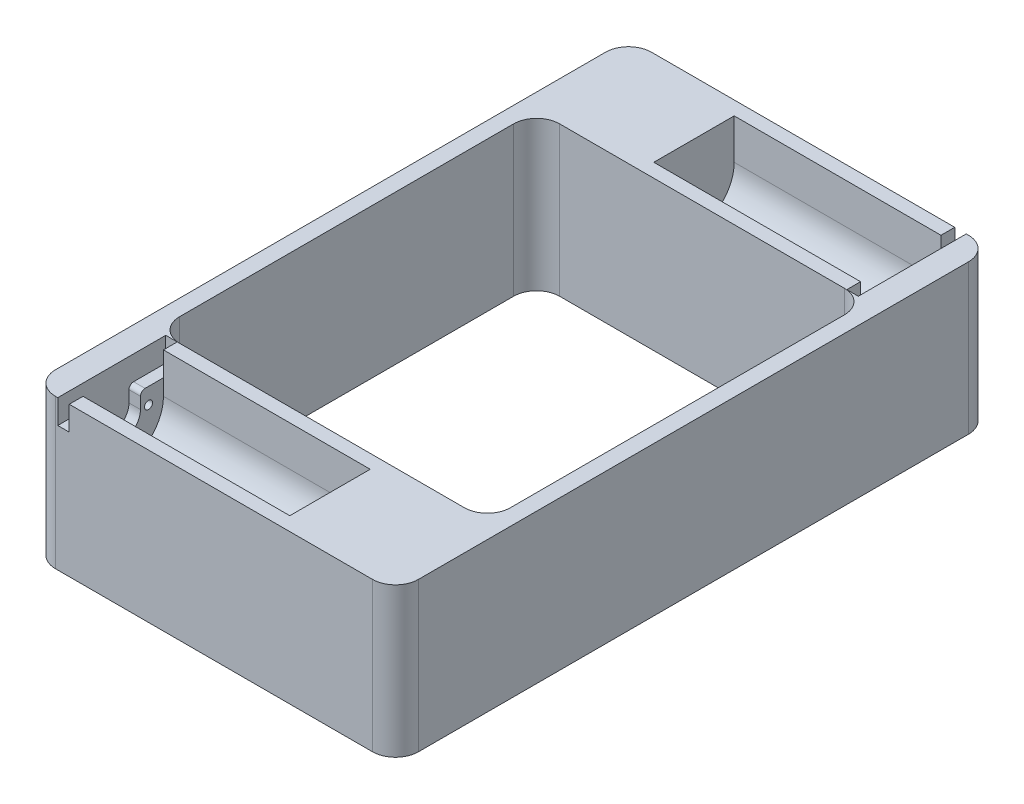
SolidWorks part; units mm, degrees
ref_plane "Front Plane" through (0, 0, 0) normal (0, 0, 1) x (1, 0, 0)
ref_plane "Top Plane" through (0, 0, 0) normal (0, 1, 0) x (1, 0, 0)
ref_plane "Right Plane" through (0, 0, 0) normal (1, 0, 0) x (0, 0, -1)
ref_axis "Center Axis" through (0, 23.7128, 0) along (0, -1, 0)
sketch "Sketch1" plane through (0, 0, 0) normal (1, 0, 0) x (0, 0, -1)
  line L0 (-159.8432, -20) -> (183.538, -20) construction
  line L1 (23.9696, -38.5304) -> (68.7681, 6.2681) construction
  line L2 (44.3566, -9.3934) -> (44.3566, -0.6434)
  line L3 (61.8566, -9.3934) -> (61.8566, -0.6434)
  line L4 (41.3566, -0.6434) -> (41.3566, -33.1434)
  line L5 (41.3566, -33.1434) -> (64.8566, -33.1434)
  line L6 (41.3566, -0.6434) -> (44.3566, -0.6434)
  line L7 (61.8566, -0.6434) -> (64.8566, -0.6434)
  line L8 (64.8566, -33.1434) -> (64.8566, -0.6434)
  arc A0 (44.3566, -9.3934) -> (61.8566, -9.3934) centre (53.1066, -9.3934) ccw
  point P1 (42.5, -20)
  dimension "D1" = 20
  dimension "D4" = 8.75
  dimension "D2" = 42.5
  dimension "D3" = 45
  dimension "D5" = 8.75
  dimension "D6" = 15
  dimension "D7" = 32.5
  dimension "D8" = 3
  dimension "D9" = 3
extrude "FrontMotorBracket" add sketch "Sketch1" along normal blind 45 from offset 13.5 offset against normal yes
sketch "Sketch8" plane through (0, 0, 0) normal (1, 0, 0) x (0, 0, -1)
  line L0 (-79.9426, -20) -> (109.5131, -20) construction
  line L1 (-68.835, 6.335) -> (-18.9148, -43.5852) construction
  line L2 (-61.8566, -9.3934) -> (-61.8566, -0.6434)
  line L3 (-64.8566, -0.6434) -> (-64.8566, -33.1434)
  line L4 (-44.3566, -0.6434) -> (-44.3566, -9.3934)
  line L5 (-64.8566, -33.1434) -> (-41.3566, -33.1434)
  line L6 (-64.8566, -0.6434) -> (-61.8566, -0.6434)
  line L7 (-44.3566, -0.6434) -> (-41.3566, -0.6434)
  line L8 (-41.3566, -33.1434) -> (-41.3566, -0.6434)
  arc A0 (-61.8566, -9.3934) -> (-44.3566, -9.3934) centre (-53.1066, -9.3934) ccw
  point P5 (-42.5, -20)
  dimension "D5" = 8.75
  dimension "D1" = 20
  dimension "D2" = 42.5
  dimension "D3" = 45
  dimension "D4" = 15
  dimension "D6" = 8.75
  dimension "D7" = 3
  dimension "D8" = 3
  dimension "D9" = 32.5
extrude "RearMotorBracket" add sketch "Sketch8" against normal blind 45 from offset 13.5 separate body
sketch "Sketch5" plane through (31.5, 0, 0) normal (1, 0, 0) x (0, 0, -1)
  line L0 (49.3566, -6.8934) -> (49.3566, -9.3934)
  line L1 (41.3566, -5.8934) -> (41.3566, -33.1434)
  line L2 (41.3566, -33.1434) -> (64.8566, -33.1434)
  line L3 (41.3566, -5.8934) -> (48.3566, -5.8934)
  line L5 (56.8566, -6.8934) -> (56.8566, -9.3934)
  line L6 (57.8566, -5.8934) -> (64.8566, -5.8934)
  line L8 (64.8566, -33.1434) -> (64.8566, -5.8934)
  arc A3 (48.3566, -5.8934) -> (49.3566, -6.8934) centre (48.3566, -6.8934) cw
  arc A4 (49.3566, -9.3934) -> (56.8566, -9.3934) centre (53.1066, -9.3934) ccw
  arc A5 (49.3566, -9.3934) -> (56.8566, -9.3934) centre (53.1066, -9.3934) ccw
  arc A6 (57.8566, -5.8934) -> (56.8566, -6.8934) centre (57.8566, -6.8934) ccw
  dimension "D3" = 1
  dimension "D4" = 1
  dimension "D2" = 3.5
  dimension "D1" = 5
extrude "FrontMotorPlate" add sketch "Sketch5" along normal blind 2.5
sketch "Sketch9" plane through (-31.5, 0, 0) normal (-1, 0, 0) x (0, 0, 1)
  line L0 (41.3566, -5.8934) -> (41.3566, -33.1434)
  line L2 (41.3566, -5.8934) -> (48.3566, -5.8934)
  line L3 (49.3566, -6.8934) -> (49.3566, -9.3934)
  line L4 (56.8566, -9.3934) -> (56.8566, -6.8934)
  line L5 (57.8566, -5.8934) -> (64.8566, -5.8934)
  line L7 (41.3566, -33.1434) -> (64.8566, -33.1434)
  line L8 (64.8566, -33.1434) -> (64.8566, -5.8934)
  arc A4 (48.3566, -5.8934) -> (49.3566, -6.8934) centre (48.3566, -6.8934) cw
  arc A5 (49.3566, -9.3934) -> (56.8566, -9.3934) centre (53.1066, -9.3934) ccw
  arc A6 (49.3566, -9.3934) -> (56.8566, -9.3934) centre (53.1066, -9.3934) ccw
  arc A7 (56.8566, -6.8934) -> (57.8566, -5.8934) centre (57.8566, -6.8934) cw
  dimension "D3" = 1
  dimension "D4" = 1
  dimension "D2" = 3.5
  dimension "D1" = 5
extrude "RearMotorPlate" add sketch "Sketch9" along normal blind 2.5
sketch "Sketch6" plane through (34, 0, 0) normal (1, 0, 0) x (0, 0, -1)
  line L0 (35.2696, -9.3934) -> (72.8501, -9.3934) construction
  line L1 (53.1066, 12.6171) -> (53.1066, -36.011) construction
  arc A0 (49.3566, -9.3934) -> (56.8566, -9.3934) centre (53.1066, -9.3934) ccw construction
  arc A1 (49.3566, -9.3934) -> (56.8566, -9.3934) centre (53.1066, -9.3934) ccw construction
  circle A2 centre (47.6066, -9.3934) radius 0.875
  circle A3 centre (58.6066, -9.3934) radius 0.875
  dimension "D2" = 1.75
  dimension "D1" = 11
extrude "FrontMotorScrewHoles" cut sketch "Sketch6" against normal up to next (2.5 mm away)
sketch "Sketch10" plane through (-34, 0, 0) normal (-1, 0, 0) x (0, 0, 1)
  line L0 (33.7961, -9.3934) -> (79.1637, -9.3934) construction
  line L1 (53.1066, 11.6109) -> (53.1066, -30.6773) construction
  arc A0 (49.3566, -9.3934) -> (56.8566, -9.3934) centre (53.1066, -9.3934) ccw construction
  arc A1 (49.3566, -9.3934) -> (56.8566, -9.3934) centre (53.1066, -9.3934) ccw construction
  circle A2 centre (47.6066, -9.3934) radius 0.875
  circle A3 centre (58.6066, -9.3934) radius 0.875
  dimension "D1" = 1.75
  dimension "D2" = 11
extrude "RearMotorScrewHoles" cut sketch "Sketch10" against normal up to next (2.5 mm away)
chamfer "FrontMotorScrewChamfer" distance 0.5 angle 45 2 edges at (34, -9.3934, -59.4816) (34, -9.3934, -48.4816)
chamfer "RearMotorScrewChamfer" distance 0.5 angle 45 2 edges at (-34, -9.3934, 59.4816) (-34, -9.3934, 48.4816)
sketch "Sketch12" plane through (0, -33.1434, 0) normal (0, -1, 0) x (-1, 0, 0)
  line L0 (-34, 41.3566) -> (13.5, 41.3566) construction
  line L1 (-36, 36.3566) -> (-36, -36.3566)
  line L2 (-34, 41.3566) -> (-34, 64.8566) construction
  line L3 (34.5, -64.8566) -> (34, -64.8566)
  line L4 (-13.5, -41.3566) -> (-31, -41.3566)
  line L5 (-39.5, 59.8566) -> (-39.5, -59.8566)
  line L6 (34, -41.3566) -> (34, -64.8566)
  line L7 (39.5, -59.8566) -> (39.5, 59.8566)
  line L8 (-34, 41.3566) -> (-34, 64.8566)
  line L9 (-34, 41.3566) -> (-31, 41.3566)
  line L10 (34, -41.3566) -> (31, -41.3566)
  line L11 (-34.5, 64.8566) -> (-34, 64.8566)
  line L12 (-13.5, -64.8566) -> (-13.5, -41.3566)
  line L13 (36, -36.3566) -> (36, 36.3566)
  line L14 (-165.3195, 0) -> (124.3922, 0) construction
  line L15 (13.5, 41.3566) -> (31, 41.3566)
  line L16 (13.5, 64.8566) -> (13.5, 41.3566)
  line L17 (13.5, 64.8566) -> (34.5, 64.8566)
  line L19 (-13.5, -64.8566) -> (-34.5, -64.8566)
  arc A0 (-31, 41.3566) -> (-36, 36.3566) centre (-31, 36.3566) ccw
  arc A1 (-31, -41.3566) -> (-36, -36.3566) centre (-31, -36.3566) cw
  arc A2 (39.5, -59.8566) -> (34.5, -64.8566) centre (34.5, -59.8566) cw
  arc A3 (-34.5, -64.8566) -> (-39.5, -59.8566) centre (-34.5, -59.8566) cw
  arc A4 (31, -41.3566) -> (36, -36.3566) centre (31, -36.3566) ccw
  arc A5 (31, 41.3566) -> (36, 36.3566) centre (31, 36.3566) cw
  arc A6 (34.5, 64.8566) -> (39.5, 59.8566) centre (34.5, 59.8566) cw
  arc A8 (-39.5, 59.8566) -> (-34.5, 64.8566) centre (-34.5, 59.8566) cw
  point P41 (0, 0)
  point P47 (0, 0)
  dimension "D2" = 5
  dimension "D3" = 5
  dimension "D4" = 0.5
  dimension "D8" = 5
  dimension "D6" = 5
  dimension "D1" = 17.5
  dimension "D5" = 2
extrude "FrameExtrude" add sketch "Sketch12" against normal blind 32.5
sketch "Sketch13" plane through (39.5, 0, 0) normal (1, 0, 0) x (0, 0, -1)
  line L0 (53.1066, -9.3934) -> (43.0852, -19.4148) construction
  line L1 (0, 0) -> (81.1646, 0) construction
  circle A0 centre (42.5, -20) radius 3.75
  arc A1 (51.3566, -12.71) -> (56.8566, -9.3934) centre (53.1066, -9.3934) ccw construction
  arc A2 (51.3566, -12.71) -> (56.8566, -9.3934) centre (53.1066, -9.3934) ccw construction
  dimension "D3" = 7.5
  dimension "D1" = 45
  dimension "D2" = 15
extrude "BearingCutRight" [suppressed] cut sketch "Sketch13" against normal blind 2.5
sketch "Sketch14" plane through (-39.5, 0, 0) normal (-1, 0, 0) x (0, 0, 1)
  line L0 (68.458, 5.958) -> (26.864, -35.636) construction
  circle A0 centre (42.5, -20) radius 3.75
  arc A2 (51.3566, -12.71) -> (56.8566, -9.3934) centre (53.1066, -9.3934) ccw construction
  arc A3 (51.3566, -12.71) -> (56.8566, -9.3934) centre (53.1066, -9.3934) ccw construction
  dimension "D2" = 7.5
  dimension "D4" = 15
extrude "BearingCutLeft" [suppressed] cut sketch "Sketch14" against normal blind 2.5
sketch "Sketch16" [suppressed] plane through (-39.5, 0, 0) normal (-1, 0, 0) x (0, 0, 1)
  circle A0 centre (-42.5, -20) radius 6.25
  circle A2 centre (42.5, -20) radius 3.75 construction
  circle A3 centre (42.5, -20) radius 3.75 construction
  dimension "D1" = 12.5
  dimension "D2" = 85
extrude "Boss-Extrude3" [suppressed] add sketch "Sketch16" along normal blind 10
sketch "Sketch17" [suppressed] plane through (-49.5, 0, 0) normal (-1, 0, 0) x (0, 0, 1)
  circle A0 centre (-42.5, -20) radius 4.25
  circle A1 centre (-42.5, -20) radius 6.25 construction
  dimension "D1" = 8.5
extrude "Cut-Extrude3" [suppressed] cut sketch "Sketch17" against normal blind 2.5
